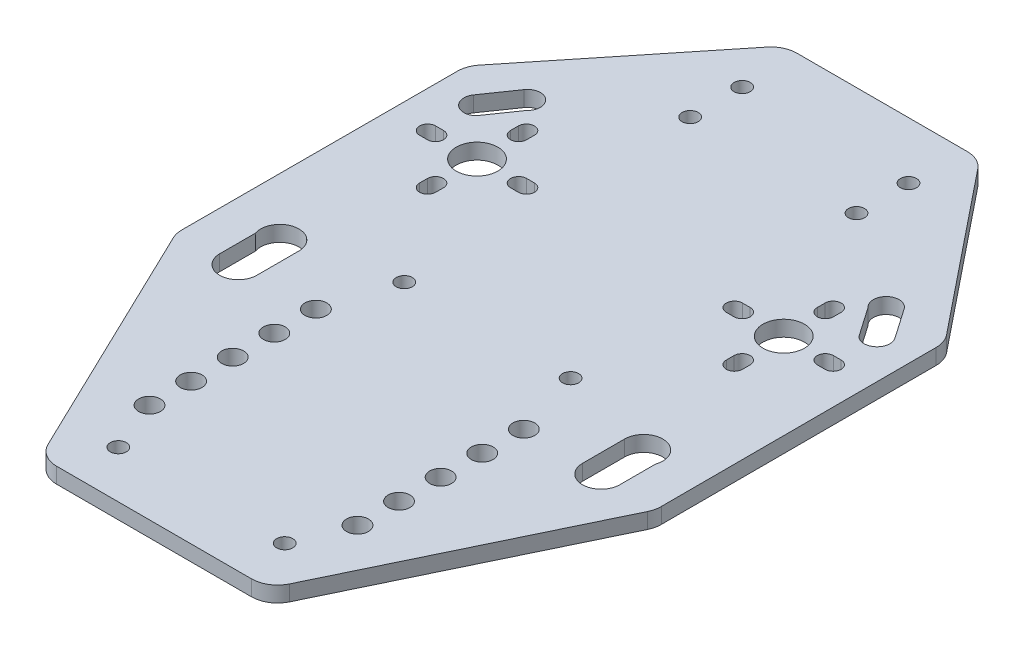
SolidWorks part; units mm, degrees
material "Thornel Mat VMA"
ref_plane "Front Plane" through (0, 0, 0) normal (0, 0, 1) x (1, 0, 0)
ref_plane "Top Plane" through (0, 0, 0) normal (0, 1, 0) x (1, 0, 0)
ref_plane "Right Plane" through (0, 0, 0) normal (1, 0, 0) x (0, 0, -1)
sketch "Sketch1" plane through (0, 0, 0) normal (0, 1, 0) x (1, 0, 0)
  line L0 (0, 0) -> (0, -27.5) construction
  line L1 (0, 0) -> (121.6069, 0) construction
  line L2 (37.5, 0) -> (39, 0) construction
  line L3 (37.5, 1.55) -> (39, 1.55)
  line L4 (37.5, -1.55) -> (39, -1.55)
  line L5 (29.5, -8) -> (29.5, -9.5) construction
  line L6 (31.05, -8) -> (31.05, -9.5)
  line L7 (27.95, -8) -> (27.95, -9.5)
  line L8 (21.5, 0) -> (20, 0) construction
  line L9 (21.5, -1.55) -> (20, -1.55)
  line L10 (21.5, 1.55) -> (20, 1.55)
  line L11 (29.5, 8) -> (29.5, 9.5) construction
  line L12 (27.95, 8) -> (27.95, 9.5)
  line L13 (31.05, 8) -> (31.05, 9.5)
  line L14 (20, -72.5) -> (20, -64.5) construction
  line L19 (-29.5, 8) -> (-29.5, 9.5) construction
  line L20 (-27.95, 8) -> (-27.95, 9.5)
  line L21 (-31.05, 8) -> (-31.05, 9.5)
  line L22 (-21.5, 0) -> (-20, 0) construction
  line L23 (-21.5, -1.55) -> (-20, -1.55)
  line L24 (-21.5, 1.55) -> (-20, 1.55)
  line L25 (-29.5, -8) -> (-29.5, -9.5) construction
  line L26 (-31.05, -8) -> (-31.05, -9.5)
  line L27 (-27.95, -8) -> (-27.95, -9.5)
  line L28 (-37.5, 0) -> (-39, 0) construction
  line L29 (-37.5, 1.55) -> (-39, 1.55)
  line L30 (-37.5, -1.55) -> (-39, -1.55)
  line L31 (-31.3246, -40.5321) -> (-31.3246, -32.4375)
  line L34 (-38.4806, -33.6183) -> (-38.4806, -40.5321)
  line L35 (31.3246, -40.5321) -> (31.3246, -32.4375)
  line L36 (38.4806, -33.6183) -> (38.4806, -40.5321)
  line L37 (-36.8266, 7.1221) -> (-32.8384, 12.8748)
  line L38 (29.5, 0) -> (50.8627, -25.4591) construction
  line L41 (46, 48.4159) -> (-46, 48.4159)
  line L44 (46, 48.4159) -> (46.1488, -91.633)
  line L47 (46.1488, -91.633) -> (-46.1487, -91.584)
  line L50 (-46, 48.4159) -> (-46.1487, -91.584)
  line L53 (-36.5402, 16.1211) -> (-40.5285, 10.3684)
  line L59 (-959, -57) -> (49041, -57) construction
  line L63 (36.8266, 7.1221) -> (32.8384, 12.8748)
  line L64 (36.5402, 16.1211) -> (40.5285, 10.3684)
  circle A0 centre (29.5, 0) radius 4
  arc A1 (37.5, 1.55) -> (37.5, -1.55) centre (37.5, 0) ccw
  arc A2 (39, -1.55) -> (39, 1.55) centre (39, 0) ccw
  arc A3 (31.05, -8) -> (27.95, -8) centre (29.5, -8) ccw
  arc A4 (27.95, -9.5) -> (31.05, -9.5) centre (29.5, -9.5) ccw
  arc A5 (21.5, -1.55) -> (21.5, 1.55) centre (21.5, 0) ccw
  arc A6 (20, 1.55) -> (20, -1.55) centre (20, 0) ccw
  arc A7 (27.95, 8) -> (31.05, 8) centre (29.5, 8) ccw
  arc A8 (31.05, 9.5) -> (27.95, 9.5) centre (29.5, 9.5) ccw
  circle A13 centre (-29.5, 0) radius 4
  arc A14 (-27.95, 8) -> (-31.05, 8) centre (-29.5, 8) cw
  arc A15 (-31.05, 9.5) -> (-27.95, 9.5) centre (-29.5, 9.5) cw
  arc A16 (-21.5, -1.55) -> (-21.5, 1.55) centre (-21.5, 0) cw
  arc A17 (-20, 1.55) -> (-20, -1.55) centre (-20, 0) cw
  arc A18 (-31.05, -8) -> (-27.95, -8) centre (-29.5, -8) cw
  arc A19 (-27.95, -9.5) -> (-31.05, -9.5) centre (-29.5, -9.5) cw
  arc A20 (-37.5, 1.55) -> (-37.5, -1.55) centre (-37.5, 0) cw
  arc A21 (-39, -1.55) -> (-39, 1.55) centre (-39, 0) cw
  circle A22 centre (16, 27.5) radius 1.55
  circle A23 centre (16, -27.5) radius 1.55
  circle A24 centre (-16, -27.5) radius 1.55
  circle A25 centre (-16, 27.5) radius 1.55
  circle A76 centre (-16, 37.5) radius 1.55
  circle A77 centre (16, 37.5) radius 1.55
  circle A78 centre (20, -72.5) radius 2.1
  circle A79 centre (-20, -72.5) radius 2.1
  circle A83 centre (-20, -40.5) radius 2.1
  circle A84 centre (20, -40.5) radius 2.1
  circle A85 centre (20, -64.5) radius 2.1
  circle A86 centre (-20, -64.5) radius 2.1
  circle A87 centre (20, -56.5) radius 2.1
  circle A88 centre (-20, -56.5) radius 2.1
  circle A89 centre (20, -48.5) radius 2.1
  circle A90 centre (-20, -48.5) radius 2.1
  circle A91 centre (-16, -82.5) radius 1.55
  circle A92 centre (16, -82.5) radius 1.55
  arc A93 (-38.4806, -40.5321) -> (-31.3246, -40.5321) centre (-34.9026, -40.5321) ccw
  arc A94 (-31.3246, -32.4375) -> (-38.4806, -33.6183) centre (-35, -32.4375) ccw
  arc A95 (38.4806, -40.5321) -> (31.3246, -40.5321) centre (34.9026, -40.5321) cw
  arc A96 (31.3246, -32.4375) -> (38.4806, -33.6183) centre (35, -32.4375) cw
  arc A103 (-40.5285, 10.3684) -> (-36.8266, 7.1221) centre (-38.4922, 8.9566) ccw
  arc A106 (-36.5402, 16.1211) -> (-32.8384, 12.8748) centre (-34.5039, 14.7093) cw
  arc A107 (36.5402, 16.1211) -> (32.8384, 12.8748) centre (34.5039, 14.7093) ccw
  arc A108 (40.5285, 10.3684) -> (36.8266, 7.1221) centre (38.4922, 8.9566) cw
  point P8 (38.25, 0)
  point P18 (29.5, -8.75)
  point P25 (20.75, 0)
  point P32 (29.5, 8.75)
  point P37 (29.5, 0)
  point P51 (0, 32.5)
  point P55 (-29.5, 8.75)
  point P62 (-20.75, 0)
  point P69 (-29.5, -8.75)
  point P76 (-38.25, 0)
  dimension "D1" = 8
  dimension "D2" = 1.55
  dimension "D4" = 8
  dimension "D5" = 4
  dimension "D6" = 92
  dimension "D7" = 140
  dimension "D8" = 2
  dimension "D9" = 59
  dimension "D10" = 3.1
  dimension "D11" = 40
  dimension "D12" = 27.5
  dimension "D13" = 8
  dimension "D15" = 7
  dimension "D27" = 4.2
  dimension "D28" = 100
  dimension "D3" = 1.5
  dimension "D14" = 35
  dimension "D16" = 7
  dimension "D23" = 50
extrude "Boss-Extrude1" [suppressed] add sketch "Sketch1" along normal blind 3
sketch "草图7" [suppressed] plane through (0, 0, 0) normal (0, 1, 0) x (1, 0, 0)
  line L0 (0, 0) -> (0, -97.058) construction
  line L1 (-27.95, -9.5) -> (-27.95, -8) construction
  line L2 (22.2054, 32.5) -> (-23.2593, 32.5) construction
  line L3 (-31.05, -8) -> (-31.05, -9.5) construction
  line L4 (-37.5, 1.55) -> (-39, 1.55)
  line L5 (-39, -1.55) -> (-37.5, -1.55)
  line L6 (-37.5, 1.55) -> (-39, 1.55)
  line L7 (-39, -1.55) -> (-37.5, -1.55)
  line L8 (-27.95, 8) -> (-27.95, 9.5)
  line L9 (-31.05, 9.5) -> (-31.05, 8)
  line L10 (-27.95, 8) -> (-27.95, 9.5)
  line L11 (-31.05, 9.5) -> (-31.05, 8)
  line L12 (-21.5, -1.55) -> (-20, -1.55)
  line L13 (-20, 1.55) -> (-21.5, 1.55)
  line L14 (-21.5, -1.55) -> (-20, -1.55)
  line L15 (-20, 1.55) -> (-21.5, 1.55)
  line L16 (-27.95, -9.5) -> (-27.95, -8)
  line L17 (-31.05, -8) -> (-31.05, -9.5)
  line L20 (37.5, -1.55) -> (39, -1.55)
  line L21 (39, 1.55) -> (37.5, 1.55)
  line L22 (37.5, -1.55) -> (39, -1.55)
  line L23 (39, 1.55) -> (37.5, 1.55)
  line L24 (27.95, -8) -> (27.95, -9.5)
  line L25 (31.05, -9.5) -> (31.05, -8)
  line L26 (27.95, -8) -> (27.95, -9.5)
  line L27 (31.05, -9.5) -> (31.05, -8)
  line L28 (21.5, 1.55) -> (20, 1.55)
  line L29 (20, -1.55) -> (21.5, -1.55)
  line L30 (21.5, 1.55) -> (20, 1.55)
  line L31 (20, -1.55) -> (21.5, -1.55)
  line L32 (31.05, 8) -> (31.05, 9.5)
  line L33 (27.95, 9.5) -> (27.95, 8)
  line L34 (31.05, 8) -> (31.05, 9.5)
  line L35 (27.95, 9.5) -> (27.95, 8)
  circle A0 centre (29.5, 0) radius 4 construction
  circle A1 centre (29.5, 0) radius 4
  circle A3 centre (-20, -72.5) radius 1.55
  circle A4 centre (-29.5, 0) radius 4
  circle A5 centre (-29.5, 0) radius 4
  circle A6 centre (16, 27.5) radius 1.55
  circle A7 centre (16, 27.5) radius 1.55
  circle A8 centre (-16, 27.5) radius 1.55
  circle A9 centre (-16, 27.5) radius 1.55
  circle A12 centre (16, 37.5) radius 1.55
  circle A13 centre (-16, 37.5) radius 1.55
  circle A14 centre (-16, -27.5) radius 1.55
  circle A15 centre (20, -72.5) radius 1.55
  arc A16 (-31.05, -9.5) -> (-27.95, -9.5) centre (-29.5, -9.5) ccw construction
  arc A18 (-37.5, -1.55) -> (-37.5, 1.55) centre (-37.5, 0) ccw
  arc A19 (-39, 1.55) -> (-39, -1.55) centre (-39, 0) ccw
  arc A20 (-37.5, -1.55) -> (-37.5, 1.55) centre (-37.5, 0) ccw
  arc A21 (-39, 1.55) -> (-39, -1.55) centre (-39, 0) ccw
  arc A23 (-27.95, -8) -> (-31.05, -8) centre (-29.5, -8) ccw construction
  arc A24 (-31.05, 8) -> (-27.95, 8) centre (-29.5, 8) ccw
  arc A25 (-27.95, 9.5) -> (-31.05, 9.5) centre (-29.5, 9.5) ccw
  arc A26 (-31.05, 8) -> (-27.95, 8) centre (-29.5, 8) ccw
  arc A27 (-27.95, 9.5) -> (-31.05, 9.5) centre (-29.5, 9.5) ccw
  arc A28 (-21.5, 1.55) -> (-21.5, -1.55) centre (-21.5, 0) ccw
  arc A29 (-20, -1.55) -> (-20, 1.55) centre (-20, 0) ccw
  arc A30 (-21.5, 1.55) -> (-21.5, -1.55) centre (-21.5, 0) ccw
  arc A31 (-20, -1.55) -> (-20, 1.55) centre (-20, 0) ccw
  arc A32 (-31.05, -9.5) -> (-27.95, -9.5) centre (-29.5, -9.5) ccw
  arc A33 (-27.95, -8) -> (-31.05, -8) centre (-29.5, -8) ccw
  circle A34 centre (16, -27.5) radius 1.55
  arc A36 (37.5, 1.55) -> (37.5, -1.55) centre (37.5, 0) ccw
  arc A37 (39, -1.55) -> (39, 1.55) centre (39, 0) ccw
  arc A38 (37.5, 1.55) -> (37.5, -1.55) centre (37.5, 0) ccw
  arc A39 (39, -1.55) -> (39, 1.55) centre (39, 0) ccw
  arc A40 (31.05, -8) -> (27.95, -8) centre (29.5, -8) ccw
  arc A41 (27.95, -9.5) -> (31.05, -9.5) centre (29.5, -9.5) ccw
  arc A42 (31.05, -8) -> (27.95, -8) centre (29.5, -8) ccw
  arc A43 (27.95, -9.5) -> (31.05, -9.5) centre (29.5, -9.5) ccw
  arc A44 (21.5, -1.55) -> (21.5, 1.55) centre (21.5, 0) ccw
  arc A45 (20, 1.55) -> (20, -1.55) centre (20, 0) ccw
  arc A46 (21.5, -1.55) -> (21.5, 1.55) centre (21.5, 0) ccw
  arc A47 (20, 1.55) -> (20, -1.55) centre (20, 0) ccw
  arc A48 (27.95, 8) -> (31.05, 8) centre (29.5, 8) ccw
  arc A49 (31.05, 9.5) -> (27.95, 9.5) centre (29.5, 9.5) ccw
  arc A50 (27.95, 8) -> (31.05, 8) centre (29.5, 8) ccw
  arc A51 (31.05, 9.5) -> (27.95, 9.5) centre (29.5, 9.5) ccw
  dimension "D4" = 3.1
  dimension "D6" = 20
  dimension "D7" = 5
  dimension "D9" = 3.1
  dimension "D16" = 32
  dimension "D17" = 55
  dimension "D5" = 100
  dimension "D8" = 0
  dimension "D1" = 0
  dimension "D2" = 0
  dimension "D3" = 0
  dimension "D10" = 0
  dimension "D11" = 0
  dimension "D12" = 0
  dimension "D13" = 0
  dimension "D14" = 0
  dimension "D15" = 0
extrude "凸台-拉伸1" add sketch "Sketch1<2>" along normal blind 3 contours L41 L50 L47 L44 A79 A78 A23 A22 A0 A2 L4 A1 L3 A4 L7 A3 L6 A6 L10 A5 L9 A8 L13 A7 L12 A13 L21 A15 L20 A14 L24 A17 L23 A16 region at (0.0029, 0, 21.6938)
sketch "Sketch1<2>" plane through (0, 0, 0) normal (0, 1, 0) x (1, 0, 0) same geometry as "Sketch1"
sketch "草图8" plane through (0, 0, 0) normal (0, 1, 0) x (1, 0, 0)
  line L0 (-17.7853, -100.1389) -> (-60.5812, -11.1827)
  line L1 (-60.5812, -11.1827) -> (-60.5812, -100.1389)
  line L2 (-60.5812, -100.1389) -> (-17.7853, -100.1389)
  line L3 (0, -21.5721) -> (0, 8.1084) construction
  line L4 (60.5812, -100.1389) -> (17.7853, -100.1389)
  line L5 (60.5812, -11.1827) -> (60.5812, -100.1389)
  line L6 (17.7853, -100.1389) -> (60.5812, -11.1827)
  line L7 (-55.5478, 2.6866) -> (-14.4304, 53.8253)
  line L8 (-14.4304, 53.8253) -> (-55.5478, 53.8253)
  line L9 (-55.5478, 53.8253) -> (-55.5478, 2.6866)
  line L10 (55.5478, 53.8253) -> (55.5478, 2.6866)
  line L11 (14.4304, 53.8253) -> (55.5478, 53.8253)
  line L12 (55.5478, 2.6866) -> (14.4304, 53.8253)
  point P14 (60.2723, -91.5971)
  point P15 (57.3671, -11.2407)
extrude "切除-拉伸1" cut sketch "草图8" along normal through all
fillet "圆角1" radius 5 8 edges at (-46.0953, 1.5, 41.2933) (-21.8948, 1.5, 91.5969) (21.8836, 1.5, 91.6202) (46.0953, 1.5, 41.2933) (46.036, 1.5, -14.5166) (18.7797, 1.5, -48.4159) (-18.7797, 1.5, -48.4159) (-46.036, 1.5, -14.5166)
